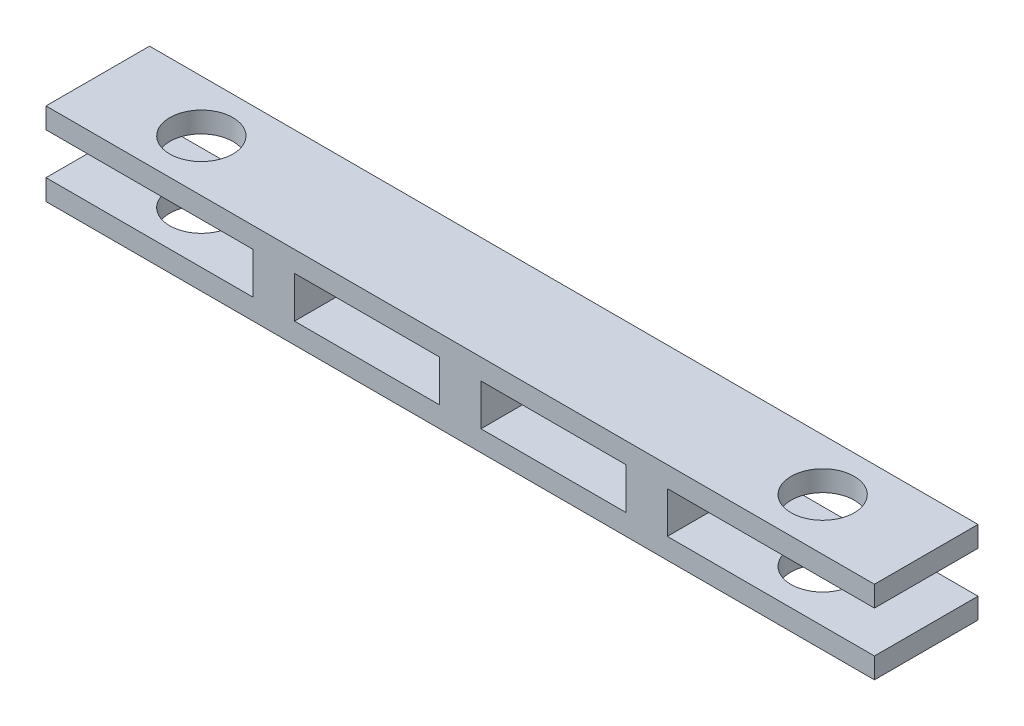
SolidWorks part; units mm, degrees
ref_plane "Front Plane" through (0, 0, 0) normal (0, 0, 1) x (1, 0, 0)
ref_plane "Top Plane" through (0, 0, 0) normal (0, 1, 0) x (1, 0, 0)
ref_plane "Right Plane" through (0, 0, 0) normal (1, 0, 0) x (0, 0, -1)
sketch "Sketch1" plane through (0, 0, 0) normal (0, 1, 0) x (1, 0, 0)
  line L1 (0, 0) -> (40, 0)
  line L2 (0, 0) -> (0, 5)
  line L3 (0, 5) -> (40, 5)
  line L4 (40, 0) -> (40, 5)
  dimension "D1" = 40
  dimension "D2" = 5
extrude "Boss-Extrude1" add sketch "Sketch1" along normal blind 4
sketch "Sketch2" plane through (0, 4, 0) normal (0, 1, 0) x (1, 0, 0)
  line L0 (0, 5) -> (0, 0) construction
  line L7 (20, 5) -> (20, 0) construction
  line L8 (40, 5) -> (0, 5) construction
  line L9 (0, 0) -> (40, 0) construction
  circle A0 centre (5, 2.5) radius 1.525
  circle A1 centre (35, 2.5) radius 1.525
  point P4 (0, 2.5)
  dimension "D1" = 3.05
  dimension "D2" = 5
extrude "Cut-Extrude1" cut sketch "Sketch2" against normal through all
sketch "Sketch3" plane through (0, 0, -5) normal (0, 0, -1) x (-1, 0, 0)
  line L0 (-40, 4) -> (-40, 0) construction
  line L1 (-40, 3) -> (-30, 3)
  line L2 (-40, 3) -> (-40, 1)
  line L3 (-40, 1) -> (-30, 1)
  line L4 (-30, 3) -> (-30, 1)
  line L5 (-20, 4) -> (-20, 0) construction
  line L6 (-28, 3) -> (-21, 3)
  line L7 (-28, 3) -> (-28, 1)
  line L8 (-28, 1) -> (-21, 1)
  line L9 (-21, 3) -> (-21, 1)
  line L14 (-40, 4) -> (0, 4) construction
  line L15 (-40, 0) -> (0, 0) construction
  line L16 (-19, 3) -> (-19, 1)
  line L17 (-12, 1) -> (-19, 1)
  line L18 (-12, 3) -> (-12, 1)
  line L19 (-12, 3) -> (-19, 3)
  line L20 (-10, 3) -> (-10, 1)
  line L21 (0, 1) -> (-10, 1)
  line L22 (0, 3) -> (0, 1)
  line L23 (0, 3) -> (-10, 3)
  point P10 (-40, 2)
  point P11 (-40, 2)
  point P12 (-28, 2)
  point P13 (-30, 2)
  dimension "D1" = 10
  dimension "D2" = 2
  dimension "D3" = 2
  dimension "D4" = 7
extrude "Cut-Extrude2" cut sketch "Sketch3" against normal through all
equation "\"columnWidth\"= 2"
equation "\"gapWidth\"= \"riserWidth\" / 2 - \"gapFromEdge\" - ( \"columnWidth\" * \"columnNumber\" )"
equation "\"columnNumber\"= 1.5"
equation "\"gapFromEdge\"= 10"
equation "\"riserWidth\"= 40"
equation "\"D1@Sketch1\"=\"riserWidth\""
equation "\"D1@Sketch3\"=\"gapFromEdge\""
equation "\"D3@Sketch3\"=\"columnWidth\""
equation "\"D4@Sketch3\"=\"gapWidth\""
